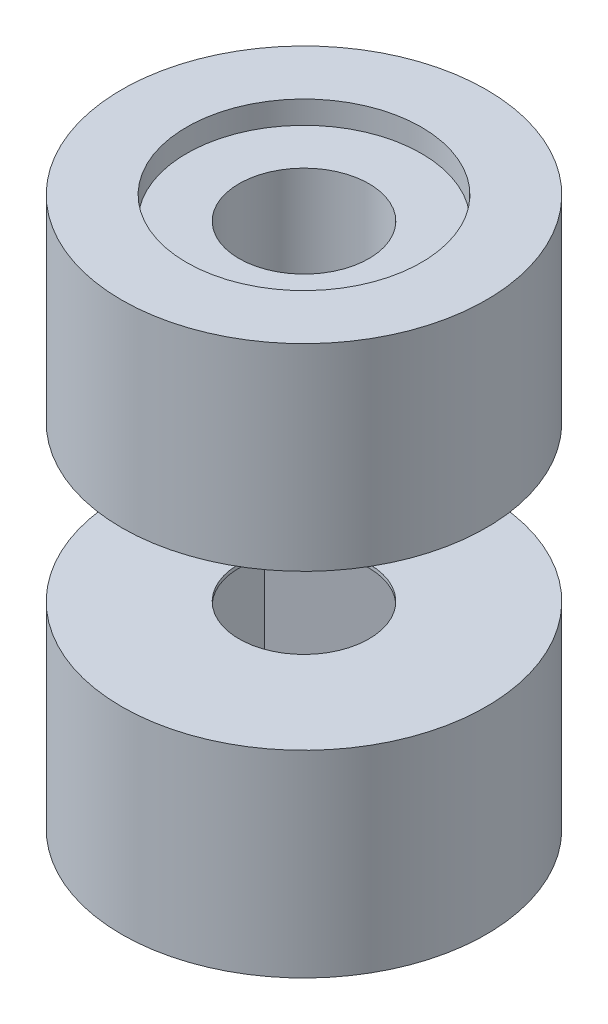
SolidWorks part; units mm, degrees
ref_plane "Front Plane" through (0, 0, 0) normal (0, 0, 1) x (1, 0, 0)
ref_plane "Top Plane" through (0, 0, 0) normal (0, 1, 0) x (1, 0, 0)
ref_plane "Right Plane" through (0, 0, 0) normal (1, 0, 0) x (0, 0, -1)
sketch "Sketch1" plane through (0, 0, 0) normal (0, 1, 0) x (1, 0, 0)
  circle A0 centre (0, 0) radius 8
extrude "Boss-Extrude1" add sketch "Sketch1" along normal blind 24.11
sketch "Sketch2" plane through (0, 0, 0) normal (0, 0, 1) x (1, 0, 0)
  line L0 (-10.2, 8.655) -> (10.2, 8.655)
  line L1 (10.2, 8.655) -> (10.2, 15.455)
  line L2 (10.2, 15.455) -> (-10.2, 15.455)
  line L3 (-10.2, 15.455) -> (-10.2, 8.655)
extrude "Cut-Extrude1" cut sketch "Sketch2" against normal through all and the other way through all
sketch "Sketch3" plane through (0, 0, 0) normal (0, 1, 0) x (1, 0, 0)
  circle A0 centre (0, 0) radius 2.85
extrude "Cut-Extrude2" cut sketch "Sketch3" along normal blind 24.11
ref_plane "Plane1" through (0, 24.11, 0) normal (0, 1, 0) x (1, 0, 0)
sketch "Sketch4" plane through (0, 24.11, 0) normal (0, 1, 0) x (1, 0, 0)
  circle A0 centre (0, 0) radius 5.15
extrude "Cut-Extrude3" cut sketch "Sketch4" against normal blind 1
sketch "Sketch5" plane through (0, 0, 0) normal (0, 1, 0) x (1, 0, 0)
  line L0 (4.1, -2.3671) -> (0, -4.7343)
  line L1 (0, -4.7343) -> (-4.1, -2.3671)
  line L2 (-4.1, -2.3671) -> (-4.1, 2.3671)
  line L3 (-4.1, 2.3671) -> (0, 4.7343)
  line L4 (0, 4.7343) -> (4.1, 2.3671)
  line L5 (4.1, 2.3671) -> (4.1, -2.3671)
extrude "Cut-Extrude4" cut sketch "Sketch5" along normal blind 8.5
